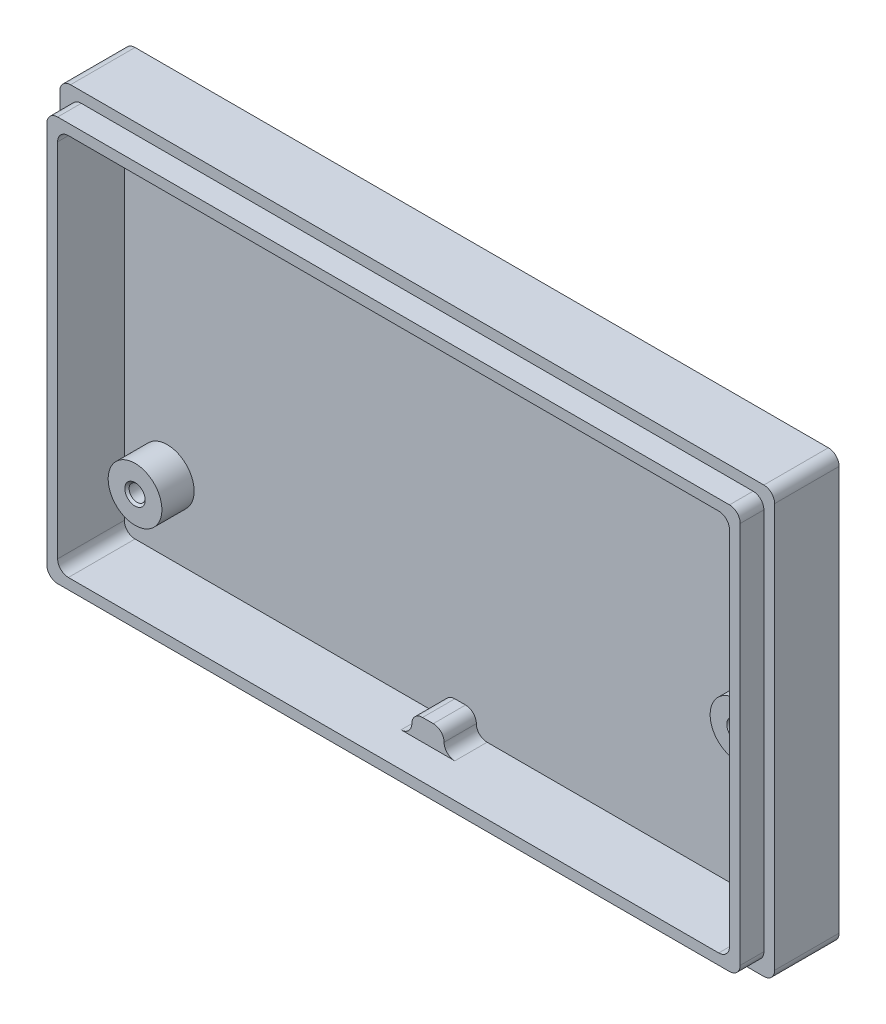
SolidWorks part; units mm, degrees
ref_plane "Front Plane" through (0, 0, 0) normal (0, 0, 1) x (1, 0, 0)
ref_plane "Top Plane" through (0, 0, 0) normal (0, 1, 0) x (1, 0, 0)
ref_plane "Right Plane" through (0, 0, 0) normal (1, 0, 0) x (0, 0, -1)
sketch "Sketch4" plane through (0, 0, 0) normal (0, 0, 1) x (1, 0, 0)
  line L0 (30.75, 34.6) -> (30.75, 0) construction
  line L1 (0, 0) -> (61.5, 0) construction
  line L2 (0, 0) -> (0, 34.6) construction
  line L3 (0, 34.6) -> (61.5, 34.6) construction
  line L4 (61.5, 0) -> (61.5, 34.6) construction
  line L5 (30.75, 17.3) -> (61.5, 17.3) construction
  line L7 (-2.5, -2.5) -> (64, -2.5)
  line L8 (-2.5, -2.5) -> (-2.5, 37.1)
  line L9 (-2.5, 37.1) -> (64, 37.1)
  line L10 (64, -2.5) -> (64, 37.1)
  line L11 (-2.5, -2.5) -> (64, 37.1) construction
  line L12 (-2.5, 37.1) -> (64, -2.5) construction
  dimension "D1" = 34.6
  dimension "D2" = 61.5
  dimension "D3" = 2.5
  dimension "D4" = 2.5
  dimension "D5" = 39.6
  dimension "D6" = 66.5
extrude "Boss-Extrude4" add sketch "Sketch4" along normal blind 2
sketch "Sketch5" plane through (0, 0, 2) normal (0, 0, 1) x (1, 0, 0)
  line L0 (64, -2.5) -> (64, 37.1) construction
  line L1 (-2.5, -2.5) -> (64, -2.5) construction
  line L2 (-2.5, 37.1) -> (-2.5, -2.5) construction
  line L3 (64, 37.1) -> (-2.5, 37.1) construction
  line L4 (64, -2.5) -> (64, 37.1)
  line L5 (-2.5, -2.5) -> (64, -2.5)
  line L6 (-2.5, 37.1) -> (-2.5, -2.5)
  line L7 (64, 37.1) -> (-2.5, 37.1)
  line L8 (62, 35.1) -> (-0.5, 35.1)
  line L9 (-0.5, 35.1) -> (-0.5, -0.5)
  line L10 (-0.5, -0.5) -> (62, -0.5)
  line L11 (62, -0.5) -> (62, 35.1)
  dimension "D1" = 2
extrude "Boss-Extrude5" add sketch "Sketch5" along normal blind 4
ref_plane "Plane1" through (30.75, 0, 0) normal (-1, 0, 0) x (0, 0, 1)
ref_plane "Plane2" through (0, 17.3, 0) normal (0, -1, 0) x (-1, 0, 0)
sketch "Sketch6" plane through (0, 0, 2) normal (0, 0, 1) x (1, 0, 0)
  line L0 (61.5, 0) -> (0, 0) construction
  line L1 (0, 0) -> (0, 34.6) construction
  line L2 (0, 34.6) -> (61.5, 34.6) construction
  line L3 (61.5, 34.6) -> (61.5, 0) construction
  line L4 (30.75, -2.5) -> (30.75, 0) construction
  line L5 (-2.5, -2.5) -> (64, -2.5) construction
  line L6 (0, 17.3) -> (-2.5, 17.3) construction
  line L7 (-2.5, 37.1) -> (-2.5, -2.5) construction
  line L8 (59.5, 12.6) -> (62, 12.6)
  line L9 (62, 12.6) -> (62, 17.6)
  line L10 (62, 17.6) -> (59.5, 17.6)
  line L11 (62, -0.5) -> (62, 35.1) construction
  arc A0 (59.5, 17.6) -> (59.5, 12.6) centre (59.5, 15.1) ccw
  circle A1 centre (3.5, 6.1) radius 2.5
  dimension "D3" = 5
  dimension "D4" = 19.5
  dimension "D5" = 2
  dimension "D6" = 56
  dimension "D7" = 9
  dimension "D1" = 61.5
  dimension "D2" = 34.6
extrude "Boss-Extrude8" add sketch "Sketch6" along normal blind 3
sketch "Sketch7" plane through (0, 0, 5) normal (0, 0, 1) x (1, 0, 0)
  circle A0 centre (59.5, 15.1) radius 0.75
  circle A1 centre (3.5, 6.1) radius 0.75
  arc A2 (59.5, 17.6) -> (59.5, 12.6) centre (59.5, 15.1) ccw construction
  circle A3 centre (3.5, 6.1) radius 2.5 construction
  dimension "D1" = 1.5
extrude "Cut-Extrude1" cut sketch "Sketch7" against normal blind 2
sketch "Sketch9" plane through (0, 0, 6) normal (0, 0, 1) x (1, 0, 0)
  line L0 (-0.5, 35.1) -> (-0.5, -0.5) construction
  line L1 (62, 35.1) -> (-0.5, 35.1) construction
  line L2 (62, -0.5) -> (62, 35.1) construction
  line L3 (-0.5, -0.5) -> (62, -0.5) construction
  line L4 (-0.5, 35.1) -> (-0.5, -0.5)
  line L5 (62, 35.1) -> (-0.5, 35.1)
  line L6 (62, -0.5) -> (62, 35.1)
  line L7 (-0.5, -0.5) -> (62, -0.5)
  line L8 (63, -1.5) -> (63, 36.1)
  line L9 (63, 36.1) -> (-1.5, 36.1)
  line L10 (-1.5, 36.1) -> (-1.5, -1.5)
  line L11 (-1.5, -1.5) -> (63, -1.5)
  dimension "D1" = 1
extrude "Boss-Extrude9" add sketch "Sketch9" along normal blind 2.2
chamfer "Chamfer1" distance 0.2 angle 45 1 edges at (4.25, 6.1, 5)
chamfer "Chamfer2" distance 0.2 angle 45 1 edges at (60.25, 15.1, 5)
sketch "Sketch11" plane through (0, 0, 2) normal (0, 0, 1) x (1, 0, 0)
  line L0 (62, 35.1) -> (-0.5, 35.1) construction
  line L1 (2.5, 35.1) -> (5.5, 35.1)
  line L2 (2.5, 35.1) -> (2.5, 33.1)
  line L3 (2.5, 33.1) -> (5.5, 33.1)
  line L4 (5.5, 35.1) -> (5.5, 33.1)
  line L5 (-0.5, -0.5) -> (62, -0.5) construction
  line L6 (29.25, 35.1) -> (32.25, 35.1)
  line L7 (29.25, 35.1) -> (29.25, 33.1)
  line L8 (29.25, 33.1) -> (32.25, 33.1)
  line L9 (32.25, 35.1) -> (32.25, 33.1)
  line L10 (56, 35.1) -> (59, 35.1)
  line L11 (56, 35.1) -> (56, 33.1)
  line L12 (56, 33.1) -> (59, 33.1)
  line L13 (59, 35.1) -> (59, 33.1)
  line L14 (29.25, -0.5) -> (32.25, -0.5)
  line L15 (29.25, -0.5) -> (29.25, 1.5)
  line L16 (29.25, 1.5) -> (32.25, 1.5)
  line L17 (32.25, -0.5) -> (32.25, 1.5)
  line L18 (-0.5, 35.1) -> (-0.5, -0.5) construction
  line L19 (62, -0.5) -> (62, 35.1) construction
  line L20 (30.75, 33.1) -> (30.75, 35.1) construction
  point P20 (2.5, 34.1)
  dimension "D1" = 3
  dimension "D2" = 2
  dimension "D3" = 3
  dimension "D4" = 3
  dimension "D5" = 2
extrude "Boss-Extrude10" add sketch "Sketch11" along normal up to surface (3 mm away) up to face at (4.45, 6.1, 5)
fillet "Fillet1" radius 1 30 edges at (-1.5, 36.1, 7.1) (-2.5, 37.1, 3) (-1.5, -1.5, 7.1) (-2.5, -2.5, 3) (63, 36.1, 7.1) (63, -1.5, 7.1) (64, -2.5, 3) (64, 37.1, 3) (-0.5, -0.5, 5.1) (-0.5, 35.1, 5.1) (62, -0.5, 5.1) (62, 35.1, 5.1) (62, 12.6, 3.5) (62, 17.6, 3.5) (32.25, -0.5, 3.5) (29.25, -0.5, 3.5) (56, 35.1, 3.5) (59, 35.1, 3.5) (32.25, 35.1, 3.5) (29.25, 35.1, 3.5) (5.5, 35.1, 3.5) (2.5, 35.1, 3.5) (29.25, 1.5, 3.5) (32.25, 1.5, 3.5) (59, 33.1, 3.5) (56, 33.1, 3.5) (32.25, 33.1, 3.5) (29.25, 33.1, 3.5) (5.5, 33.1, 3.5) (2.5, 33.1, 3.5)
equation "\"D4@Sketch4\"=\"D3@Sketch4\""
equation "\"D5@Sketch11\"=\"D2@Sketch11\""
